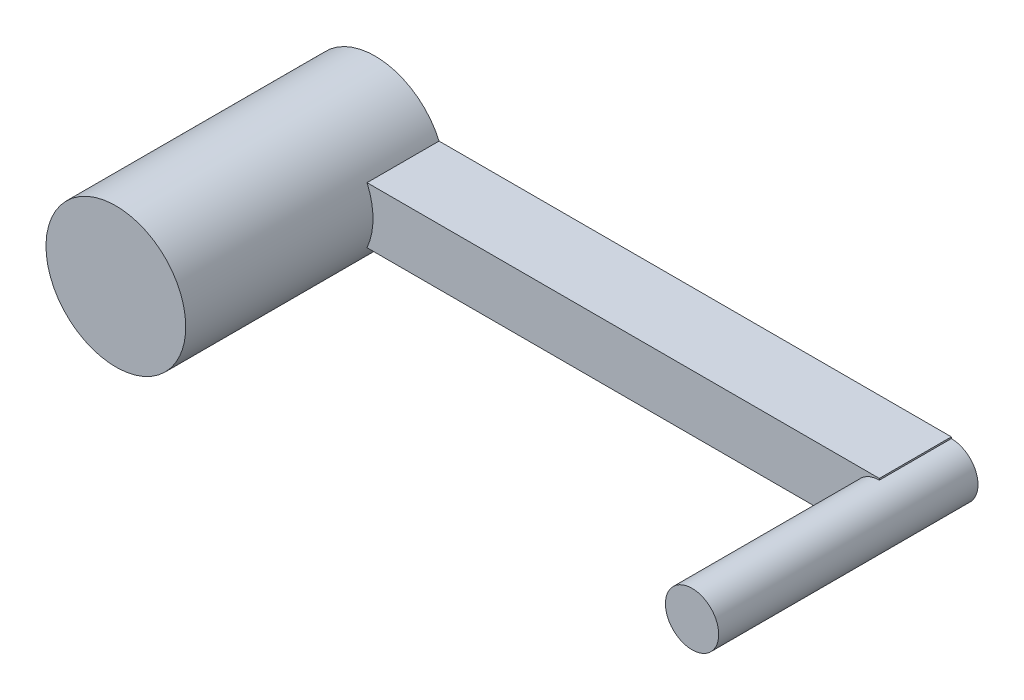
SolidWorks part; units mm, degrees
ref_plane "Front Plane" through (0, 0, 0) normal (0, 0, 1) x (1, 0, 0)
ref_plane "Top Plane" through (0, 0, 0) normal (0, 1, 0) x (1, 0, 0)
ref_plane "Right Plane" through (0, 0, 0) normal (1, 0, 0) x (0, 0, -1)
sketch "Sketch1" plane through (0, 0, 0) normal (0, 0, 1) x (1, 0, 0)
  line L1 (0, 0) -> (40, 0)
  line L2 (0, 0) -> (0, -3.913)
  line L3 (0, -3.913) -> (40, -3.913)
  line L4 (40, 0) -> (40, -3.913)
  circle A0 centre (0, -1.9565) radius 4.85
  circle A1 centre (40, -1.9565) radius 1.85
  point P9 (0, 0)
  dimension "D2" = 9.7
  dimension "D3" = 3.7
  dimension "D1" = 40
extrude "Boss-Extrude1" add sketch "Sketch1" along normal blind 5 contours A1 L1 A0 L3 region at (21.6743, -1.9565, 0)
extrude "Boss-Extrude2" add sketch "Sketch1<3>" along normal blind 18 contours L1 A0 L3 L2 | L3 A0 L1 L2 | L4 A1 | L4 A1 region at (-0.785, -1.9565, 0) region at (2.3591, -1.9565, 0) region at (40.7852, -1.9565, 0) region at (39.2148, -1.9565, 0)
sketch "Sketch1<3>" plane through (0, 0, 0) normal (0, 0, 1) x (1, 0, 0) same geometry as "Sketch1"
